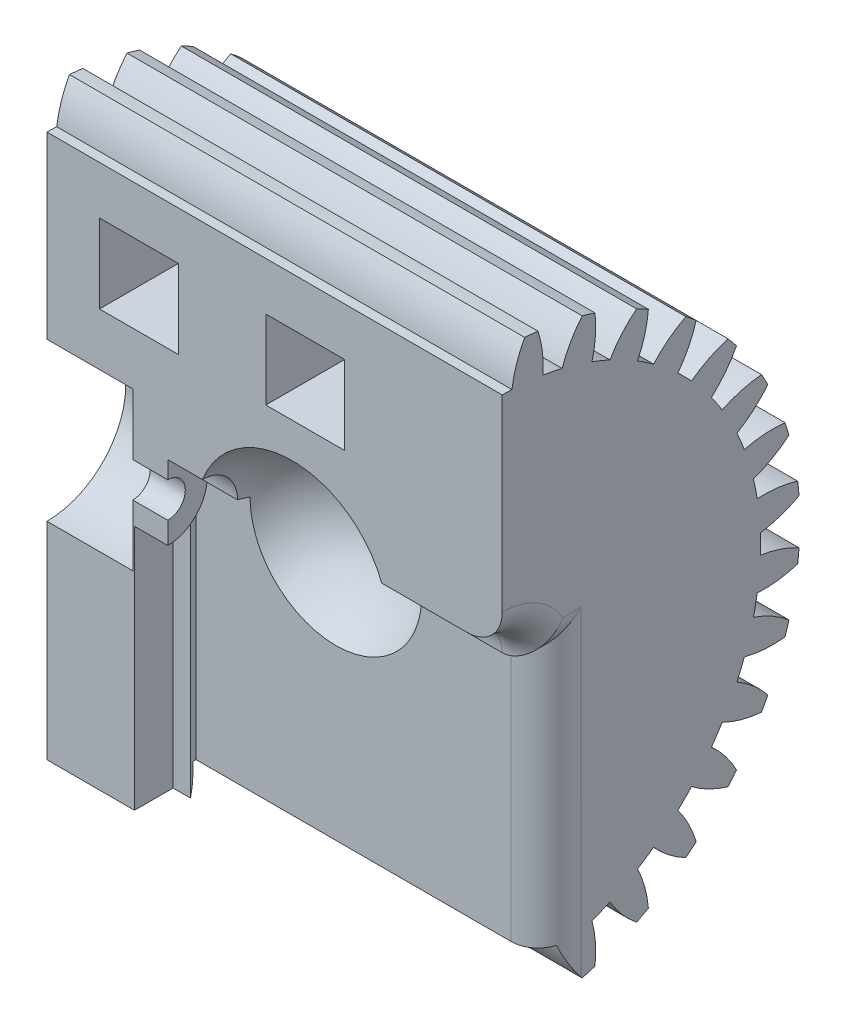
SolidWorks part; units mm, degrees
ref_plane "Plane1" through (0, 0, 0) normal (0, 0, 1) x (1, 0, 0)
ref_plane "Plane2" through (0, 0, 0) normal (0, 1, 0) x (1, 0, 0)
ref_plane "Plane3" through (0, 0, 0) normal (1, 0, 0) x (0, 0, -1)
other "Configuration Table"
sketch "HoldingSke" plane through (0, 0, 0) normal (0, 1, 0) x (1, 0, 0)
  line L0 (0, 0) -> (1.6961, -1.0598)
  line L1 (-15, 0) -> (100, 0) construction
  line L2 (0, 0) -> (-2.1039, 2.3779)
  line L3 (0, 0) -> (-11.863, 4.5341)
  line L4 (0, 0) -> (7.3237, 4.5764)
  line L5 (0, 0) -> (-46.8476, -17.4728)
  line L6 (0, 0) -> (-8.2896, -5.593)
  line L7 (-2.1039, 2.3779) -> (8.6586, 51.2059)
  line L8 (-76.2, 54.61) -> (-75.9, 54.61)
  line L9 (-67.7845, 28.3722) -> (-49.3413, 33.142)
  line L10 (-76.2, 71.12) -> (104.1128, 71.12)
  line L11 (0, 0) -> (-10, 0)
  line L12 (-76.2, 101.6) -> (-76.181, 101.6)
  line L13 (24.9733, 27.94) -> (52.9518, 28.4284)
  line L14 (24.9733, 27.94) -> (24.9743, 27.94)
  line L15 (24.9733, 27.94) -> (100.4006, 29.5858)
  line L16 (-63.627, -0.5) -> (-12.827, -0.5)
  circle A0 centre (0, 0) radius 1
  circle A1 centre (0, 0) radius 7.374
  circle A2 centre (0, 0) radius 37.5
  circle A3 centre (0, 0) radius 1
  dimension "Num_teeth" = 32
  dimension "Pitch_radius" = 180.3128
  dimension "Width" = 10
  dimension "Thickness" = 10
sketch "BasProSke" plane through (0, 0, 0) normal (0, 1, 0) x (1, 0, 0)
  line L0 (-10, 0) -> (60, 0) construction
  line L1 (0, 0) -> (0, 8.5)
  line L2 (0, 0) -> (10, 0)
  line L3 (10, 0) -> (10, 8.5)
  line L4 (10, 8.5) -> (0, 8.5)
  dimension "Thickness" = 10
  dimension "Diameter" = 17
revolve "Base-Revolve" add sketch "BasProSke" angle 360 about L0
sketch "TooCutSke" plane through (0, 0, 0) normal (1, 0, 0) x (0, 0, -1)
  line L1 (0, 0) -> (0, 107) construction
  line L2 (0, 0) -> (-0.4258, 7.9887) construction
  line L3 (0, 0) -> (-1.5667, 15.9069) construction
  line L4 (-0.4258, 7.9887) -> (-0.7833, 7.9534) construction
  arc A0 (0.277, 7.3688) -> (-0.277, 7.3688) centre (0, 0) ccw
  arc A1 (0.6561, 8.5001) -> (-0.6561, 8.5001) centre (0, 0) ccw
  circle A2 centre (0, 0) radius 8 construction
  circle A3 centre (0, 0) radius 7.7452 construction
  arc A4 (-0.277, 7.3688) -> (-0.6561, 8.5001) centre (-3.4475, 6.9356) ccw
  arc A5 (0.6561, 8.5001) -> (0.277, 7.3688) centre (3.4475, 6.9356) ccw
extrude "ToothCut" cut sketch "TooCutSke" along normal through all
fillet "Breaks" [suppressed] radius 0.01 tangent propagation no
fillet "RootFillets" [suppressed] radius 0.126
pattern_circular "TeethCuts" count 32 every 11.25 about axis through (-10, 0, 0) along (1, 0, 0) of "ToothCut", "RootFillets", "Breaks"
sketch "HubNeaOneSke" plane through (0, 0, 0) normal (-1, 0, 0) x (0, 0, 1)
  circle A0 centre (0, 0) radius 7.374
  dimension "Diameter" = 14.748
extrude "HubNearOne" [suppressed] add sketch "HubNeaOneSke" along normal blind 40.0001
sketch "HubNeaBotSke" plane through (0, 0, 0) normal (-1, 0, 0) x (0, 0, 1)
  circle A0 centre (0, 0) radius 7.374
  dimension "Diameter" = 14.748
extrude "HubNearBoth" [suppressed] add sketch "HubNeaBotSke" along normal blind 20
ref_plane "FarPln" through (10, 0, 0) normal (1, 0, 0) x (0, 0, -1)
sketch "HubFarSke" plane through (10, 0, 0) normal (1, 0, 0) x (0, 0, -1)
  circle A0 centre (0, 0) radius 7.374
  dimension "Diameter" = 14.748
extrude "HubFar" [suppressed] add sketch "HubFarSke" along normal blind 20
sketch "BorSke" plane through (0, 0, 0) normal (1, 0, 0) x (0, 0, -1)
  circle A0 centre (0, 0) radius 1
  dimension "Diameter" = 2
extrude "Bore" cut sketch "BorSke" along normal mid plane 100.0001
sketch "KeySke" plane through (0, 0, 0) normal (1, 0, 0) x (0, 0, -1)
  line L0 (-0.4, 0) -> (-0.4, 1.3)
  line L1 (-0.4, 1.3) -> (0.4, 1.3)
  line L2 (0.4, 1.3) -> (0.4, 0)
  line L3 (0, 0) -> (0, 34) construction
  line L4 (-0.4, 0) -> (0.4, 0)
  dimension "Width" = 0.8
extrude "Keyway" [suppressed] cut sketch "KeySke" along normal mid plane 100.0001
pattern_circular "Keyway2" [suppressed] count 2 every 90 about axis through (-10, 0, 0) along (1, 0, 0) reverse direction yes
sketch "Sketch1" plane through (10, 0, 0) normal (1, 0, 0) x (0, 0, -1)
  line L1 (-1.1, 0) -> (1.1, 0)
  line L2 (-1.1, 0) -> (-1.1, -12)
  line L3 (-1.1, -12) -> (1.1, -12)
  line L4 (1.1, 0) -> (1.1, -12)
  circle A0 centre (0, 0) radius 1 construction
  dimension "D3" = 12
  dimension "D1" = 2.2
  dimension "D2" = 1.1
  dimension "D4" = 12
extrude "Cut-Extrude1" cut sketch "Sketch1" against normal through all
sketch "Sketch2" plane through (0, 0, 0) normal (0, 0, 1) x (1, 0, 0)
  line L3 (4.25, 0) -> (9.75, 0)
  arc A0 (9.75, 0) -> (4.25, 0) centre (7, 0) ccw
  dimension "D2" = 5.5
  dimension "D1" = 7
revolve "Cut-Revolve1" cut sketch "Sketch2" angle 360 about L3
ref_plane "Plane4" through (3, 0, 0) normal (-1, 0, 0) x (0, 0, 1)
sketch "Sketch4" plane through (3, 0, 0) normal (-1, 0, 0) x (0, 0, 1)
  circle A0 centre (0, 0) radius 1.125
  circle A1 centre (0, 0) radius 0.5
  dimension "D1" = 1
extrude "Boss-Extrude1" add sketch "Sketch4" along normal blind 0.5
sketch "Sketch5" plane through (0, 0, -1.1) normal (0, 0, 1) x (1, 0, 0)
  line L0 (0, -8.1488) -> (10, -8.1488) construction
  line L1 (0, 0) -> (2.5, 0)
  line L2 (0, 0) -> (0, -8.1488)
  line L3 (0, -8.1488) -> (2.5, -8.1488)
  line L4 (2.5, 0) -> (2.5, -8.1488)
  dimension "D1" = 2.5
extrude "Boss-Extrude2" add sketch "Sketch5" along normal up to next
sketch "Sketch6" plane through (0, 0, 0) normal (-1, 0, 0) x (0, 0, 1)
  line L0 (1, 0) -> (-1, 0) construction
  circle A0 centre (0, 0) radius 2.25
  dimension "D1" = 4.5
extrude "Cut-Extrude4" cut sketch "Sketch6" against normal blind 2.45
sketch "Sketch7" plane through (2.5, 0, 0) normal (1, 0, 0) x (0, 0, -1)
  circle A0 centre (0, 0) radius 0.5
extrude "Cut-Extrude5" cut sketch "Sketch7" against normal blind 2.4
sketch "Sketch8" plane through (0, 0, 0) normal (0, 0, 1) x (1, 0, 0)
  line L1 (-0.5092, 8.9097) -> (10.5538, 8.9097)
  line L2 (-0.5092, 8.9097) -> (-0.5092, -8.8891)
  line L3 (-0.5092, -8.8891) -> (10.5538, -8.8891)
  line L4 (10.5538, 8.9097) -> (10.5538, -8.8891)
extrude "Cut-Extrude7" cut sketch "Sketch8" along normal blind 10
sketch "Sketch9" plane through (0, 0, 0) normal (0, 0, 1) x (1, 0, 0)
  line L0 (10, 1) -> (10, 7.374) construction
  line L1 (1.5, 6) -> (3.75, 6)
  line L2 (1.5, 6) -> (1.5, 3.75)
  line L3 (1.5, 3.75) -> (3.75, 3.75)
  line L4 (3.75, 6) -> (3.75, 3.75)
  line L5 (6.25, 6) -> (8.5, 6)
  line L6 (6.25, 6) -> (6.25, 3.75)
  line L7 (6.25, 3.75) -> (8.5, 3.75)
  line L8 (8.5, 6) -> (8.5, 3.75)
  line L9 (0, 7.374) -> (0, 2.25) construction
  line L10 (0, 2.25) -> (0, -2.25) construction
  point P14 (0, 0)
  dimension "D1" = 2.25
  dimension "D2" = 2.25
  dimension "D3" = 2.25
  dimension "D4" = 2.25
  dimension "D5" = 1.5
  dimension "D6" = 1.5
  dimension "D7" = 3.75
  dimension "D8" = 3.75
extrude "Cut-Extrude8" cut sketch "Sketch9" against normal blind 2.25
sketch "Sketch10" plane through (10, 0, 0) normal (1, 0, 0) x (0, 0, -1)
  line L1 (0, 0) -> (1.25, 0)
  line L2 (0, 0) -> (0, -9)
  line L3 (0, -9) -> (1.25, -9)
  line L4 (1.25, 0) -> (1.25, -9)
  dimension "D1" = 1.25
  dimension "D2" = 9
extrude "Cut-Extrude10" cut sketch "Sketch10" against normal blind 7 contours L2 L1 L4 L3
ref_plane "Plane5" through (12, 0, 0) normal (1, 0, 0) x (0, 0, -1)
sketch "Sketch11" plane through (12, 0, 0) normal (1, 0, 0) x (0, 0, -1)
  line L0 (0, 1) -> (0, 7.374) construction
  line L1 (1.25, 0) -> (1, 0) construction
  line L2 (1.25, 0) -> (1.25, -7.2673) construction
  line L3 (0, 1) -> (0, 7.374)
  line L4 (1.25, 0) -> (1, 0)
  line L5 (1.25, 0) -> (1.25, -7.2673)
  arc A0 (2.564, 6.9139) -> (2.6499, 8.0764) centre (-0.531, 7.727) ccw construction
  arc A1 (8.0764, -2.6499) -> (8.1875, -2.2837) centre (0, 0) ccw construction
  arc A2 (8.4382, -1.0233) -> (8.4757, -0.6425) centre (0, 0) ccw construction
  arc A3 (8.1875, 2.2837) -> (8.0764, 2.6499) centre (0, 0) ccw construction
  arc A4 (7.5846, 3.8371) -> (7.4042, 4.1746) centre (0, 0) ccw construction
  arc A5 (6.6903, 5.2431) -> (6.4475, 5.5389) centre (0, 0) ccw construction
  arc A6 (5.5389, 6.4475) -> (5.2431, 6.6903) centre (0, 0) ccw construction
  arc A7 (2.6499, 8.0764) -> (2.2837, 8.1875) centre (0, 0) ccw construction
  arc A8 (4.1746, 7.4042) -> (3.8371, 7.5846) centre (0, 0) ccw construction
  arc A9 (3.8371, 7.5846) -> (3.0758, 6.7019) centre (5.8392, 5.0883) ccw construction
  arc A10 (2.2837, 8.1875) -> (1.7093, 7.1732) centre (4.7344, 6.1297) ccw construction
  arc A11 (3.8636, 6.2808) -> (4.1746, 7.4042) centre (0.9867, 7.6821) ccw construction
  arc A12 (5.2431, 6.6903) -> (4.3242, 5.973) centre (6.7197, 3.8514) ccw construction
  arc A13 (5.0147, 5.4064) -> (5.5389, 6.4475) centre (2.4664, 7.342) ccw construction
  arc A14 (6.4475, 5.5389) -> (5.4064, 5.0147) centre (7.342, 2.4664) ccw construction
  arc A15 (5.973, 4.3242) -> (6.6903, 5.2431) centre (3.8514, 6.7197) ccw construction
  arc A16 (7.4042, 4.1746) -> (6.2808, 3.8636) centre (7.6821, 0.9867) ccw construction
  arc A17 (6.7019, 3.0758) -> (7.5846, 3.8371) centre (5.0883, 5.8392) ccw construction
  arc A18 (8.0764, 2.6499) -> (6.9139, 2.564) centre (7.727, -0.531) ccw construction
  arc A19 (7.1732, 1.7093) -> (8.1875, 2.2837) centre (6.1297, 4.7344) ccw construction
  arc A20 (8.4382, 1.0233) -> (7.2812, 1.1659) centre (7.4749, -2.0282) ccw construction
  arc A21 (8.4757, 0.6425) -> (8.4382, 1.0233) centre (0, 0) ccw construction
  arc A22 (7.3688, 0.277) -> (8.4757, 0.6425) centre (6.9356, 3.4475) ccw construction
  arc A23 (8.4757, -0.6425) -> (7.3688, -0.277) centre (6.9356, -3.4475) ccw construction
  arc A24 (7.2812, -1.1659) -> (8.4382, -1.0233) centre (7.4749, 2.0282) ccw construction
  arc A25 (8.1875, -2.2837) -> (7.1732, -1.7093) centre (6.1297, -4.7344) ccw construction
  arc A26 (6.9139, -2.564) -> (8.0764, -2.6499) centre (7.727, 0.531) ccw construction
  arc A27 (7.4042, -4.1746) -> (7.5846, -3.8371) centre (0, 0) ccw construction
  arc A28 (7.5846, -3.8371) -> (6.7019, -3.0758) centre (5.0883, -5.8392) ccw construction
  arc A29 (6.2808, -3.8636) -> (7.4042, -4.1746) centre (7.6821, -0.9867) ccw construction
  arc A30 (6.6903, -5.2431) -> (5.973, -4.3242) centre (3.8514, -6.7197) ccw construction
  arc A31 (6.4475, -5.5389) -> (6.6903, -5.2431) centre (0, 0) ccw construction
  arc A32 (5.4064, -5.0147) -> (6.4475, -5.5389) centre (7.342, -2.4664) ccw construction
  arc A33 (5.5389, -6.4475) -> (5.0147, -5.4064) centre (2.4664, -7.342) ccw construction
  arc A34 (5.2431, -6.6903) -> (5.5389, -6.4475) centre (0, 0) ccw construction
  arc A35 (4.3242, -5.973) -> (5.2431, -6.6903) centre (6.7197, -3.8514) ccw construction
  arc A36 (4.1746, -7.4042) -> (3.8636, -6.2808) centre (0.9867, -7.6821) ccw construction
  arc A37 (3.8371, -7.5846) -> (4.1746, -7.4042) centre (0, 0) ccw construction
  arc A38 (3.0758, -6.7019) -> (3.8371, -7.5846) centre (5.8392, -5.0883) ccw construction
  arc A39 (2.6499, -8.0764) -> (2.564, -6.9139) centre (-0.531, -7.727) ccw construction
  arc A40 (2.2837, -8.1875) -> (2.6499, -8.0764) centre (0, 0) ccw construction
  arc A41 (1.7093, -7.1732) -> (2.2837, -8.1875) centre (4.7344, -6.1297) ccw construction
  arc A42 (1.25, -7.2673) -> (1.7093, -7.1732) centre (0, 0) ccw construction
  arc A43 (2.564, -6.9139) -> (3.0758, -6.7019) centre (0, 0) ccw construction
  arc A44 (3.8636, -6.2808) -> (4.3242, -5.973) centre (0, 0) ccw construction
  arc A45 (5.0147, -5.4064) -> (5.4064, -5.0147) centre (0, 0) ccw construction
  arc A46 (5.973, -4.3242) -> (6.2808, -3.8636) centre (0, 0) ccw construction
  arc A47 (6.7019, -3.0758) -> (6.9139, -2.564) centre (0, 0) ccw construction
  arc A48 (7.1732, -1.7093) -> (7.2812, -1.1659) centre (0, 0) ccw construction
  arc A49 (7.3688, -0.277) -> (7.3688, 0.277) centre (0, 0) ccw construction
  arc A50 (7.2812, 1.1659) -> (7.1732, 1.7093) centre (0, 0) ccw construction
  arc A51 (6.9139, 2.564) -> (6.7019, 3.0758) centre (0, 0) ccw construction
  arc A52 (6.2808, 3.8636) -> (5.973, 4.3242) centre (0, 0) ccw construction
  arc A53 (5.4064, 5.0147) -> (5.0147, 5.4064) centre (0, 0) ccw construction
  arc A54 (4.3242, 5.973) -> (3.8636, 6.2808) centre (0, 0) ccw construction
  arc A55 (3.0758, 6.7019) -> (2.564, 6.9139) centre (0, 0) ccw construction
  arc A56 (1.7093, 7.1732) -> (1.1659, 7.2812) centre (0, 0) ccw construction
  arc A57 (1.0233, 8.4382) -> (0.6425, 8.4757) centre (0, 0) ccw construction
  arc A58 (1.1659, 7.2812) -> (1.0233, 8.4382) centre (-2.0282, 7.4749) ccw construction
  arc A59 (0.6425, 8.4757) -> (0.277, 7.3688) centre (3.4475, 6.9356) ccw construction
  arc A60 (0.277, 7.3688) -> (0, 7.374) centre (0, 0) ccw construction
  arc A61 (1, 0) -> (0, 1) centre (0, 0) ccw construction
  arc A62 (2.564, 6.9139) -> (2.6499, 8.0764) centre (-0.531, 7.727) ccw
  arc A63 (8.0764, -2.6499) -> (8.1875, -2.2837) centre (0, 0) ccw
  arc A64 (8.4382, -1.0233) -> (8.4757, -0.6425) centre (0, 0) ccw
  arc A65 (8.1875, 2.2837) -> (8.0764, 2.6499) centre (0, 0) ccw
  arc A66 (7.5846, 3.8371) -> (7.4042, 4.1746) centre (0, 0) ccw
  arc A67 (6.6903, 5.2431) -> (6.4475, 5.5389) centre (0, 0) ccw
  arc A68 (5.5389, 6.4475) -> (5.2431, 6.6903) centre (0, 0) ccw
  arc A69 (2.6499, 8.0764) -> (2.2837, 8.1875) centre (0, 0) ccw
  arc A70 (4.1746, 7.4042) -> (3.8371, 7.5846) centre (0, 0) ccw
  arc A71 (3.8371, 7.5846) -> (3.0758, 6.7019) centre (5.8392, 5.0883) ccw
  arc A72 (2.2837, 8.1875) -> (1.7093, 7.1732) centre (4.7344, 6.1297) ccw
  arc A73 (3.8636, 6.2808) -> (4.1746, 7.4042) centre (0.9867, 7.6821) ccw
  arc A74 (5.2431, 6.6903) -> (4.3242, 5.973) centre (6.7197, 3.8514) ccw
  arc A75 (5.0147, 5.4064) -> (5.5389, 6.4475) centre (2.4664, 7.342) ccw
  arc A76 (6.4475, 5.5389) -> (5.4064, 5.0147) centre (7.342, 2.4664) ccw
  arc A77 (5.973, 4.3242) -> (6.6903, 5.2431) centre (3.8514, 6.7197) ccw
  arc A78 (7.4042, 4.1746) -> (6.2808, 3.8636) centre (7.6821, 0.9867) ccw
  arc A79 (6.7019, 3.0758) -> (7.5846, 3.8371) centre (5.0883, 5.8392) ccw
  arc A80 (8.0764, 2.6499) -> (6.9139, 2.564) centre (7.727, -0.531) ccw
  arc A81 (7.1732, 1.7093) -> (8.1875, 2.2837) centre (6.1297, 4.7344) ccw
  arc A82 (8.4382, 1.0233) -> (7.2812, 1.1659) centre (7.4749, -2.0282) ccw
  arc A83 (8.4757, 0.6425) -> (8.4382, 1.0233) centre (0, 0) ccw
  arc A84 (7.3688, 0.277) -> (8.4757, 0.6425) centre (6.9356, 3.4475) ccw
  arc A85 (8.4757, -0.6425) -> (7.3688, -0.277) centre (6.9356, -3.4475) ccw
  arc A86 (7.2812, -1.1659) -> (8.4382, -1.0233) centre (7.4749, 2.0282) ccw
  arc A87 (8.1875, -2.2837) -> (7.1732, -1.7093) centre (6.1297, -4.7344) ccw
  arc A88 (6.9139, -2.564) -> (8.0764, -2.6499) centre (7.727, 0.531) ccw
  arc A89 (7.4042, -4.1746) -> (7.5846, -3.8371) centre (0, 0) ccw
  arc A90 (7.5846, -3.8371) -> (6.7019, -3.0758) centre (5.0883, -5.8392) ccw
  arc A91 (6.2808, -3.8636) -> (7.4042, -4.1746) centre (7.6821, -0.9867) ccw
  arc A92 (6.6903, -5.2431) -> (5.973, -4.3242) centre (3.8514, -6.7197) ccw
  arc A93 (6.4475, -5.5389) -> (6.6903, -5.2431) centre (0, 0) ccw
  arc A94 (5.4064, -5.0147) -> (6.4475, -5.5389) centre (7.342, -2.4664) ccw
  arc A95 (5.5389, -6.4475) -> (5.0147, -5.4064) centre (2.4664, -7.342) ccw
  arc A96 (5.2431, -6.6903) -> (5.5389, -6.4475) centre (0, 0) ccw
  arc A97 (4.3242, -5.973) -> (5.2431, -6.6903) centre (6.7197, -3.8514) ccw
  arc A98 (4.1746, -7.4042) -> (3.8636, -6.2808) centre (0.9867, -7.6821) ccw
  arc A99 (3.8371, -7.5846) -> (4.1746, -7.4042) centre (0, 0) ccw
  arc A100 (3.0758, -6.7019) -> (3.8371, -7.5846) centre (5.8392, -5.0883) ccw
  arc A101 (2.6499, -8.0764) -> (2.564, -6.9139) centre (-0.531, -7.727) ccw
  arc A102 (2.2837, -8.1875) -> (2.6499, -8.0764) centre (0, 0) ccw
  arc A103 (1.7093, -7.1732) -> (2.2837, -8.1875) centre (4.7344, -6.1297) ccw
  arc A104 (1.25, -7.2673) -> (1.7093, -7.1732) centre (0, 0) ccw
  arc A105 (2.564, -6.9139) -> (3.0758, -6.7019) centre (0, 0) ccw
  arc A106 (3.8636, -6.2808) -> (4.3242, -5.973) centre (0, 0) ccw
  arc A107 (5.0147, -5.4064) -> (5.4064, -5.0147) centre (0, 0) ccw
  arc A108 (5.973, -4.3242) -> (6.2808, -3.8636) centre (0, 0) ccw
  arc A109 (6.7019, -3.0758) -> (6.9139, -2.564) centre (0, 0) ccw
  arc A110 (7.1732, -1.7093) -> (7.2812, -1.1659) centre (0, 0) ccw
  arc A111 (7.3688, -0.277) -> (7.3688, 0.277) centre (0, 0) ccw
  arc A112 (7.2812, 1.1659) -> (7.1732, 1.7093) centre (0, 0) ccw
  arc A113 (6.9139, 2.564) -> (6.7019, 3.0758) centre (0, 0) ccw
  arc A114 (6.2808, 3.8636) -> (5.973, 4.3242) centre (0, 0) ccw
  arc A115 (5.4064, 5.0147) -> (5.0147, 5.4064) centre (0, 0) ccw
  arc A116 (4.3242, 5.973) -> (3.8636, 6.2808) centre (0, 0) ccw
  arc A117 (3.0758, 6.7019) -> (2.564, 6.9139) centre (0, 0) ccw
  arc A118 (1.7093, 7.1732) -> (1.1659, 7.2812) centre (0, 0) ccw
  arc A119 (1.0233, 8.4382) -> (0.6425, 8.4757) centre (0, 0) ccw
  arc A120 (1.1659, 7.2812) -> (1.0233, 8.4382) centre (-2.0282, 7.4749) ccw
  arc A121 (0.6425, 8.4757) -> (0.277, 7.3688) centre (3.4475, 6.9356) ccw
  arc A122 (0.277, 7.3688) -> (0, 7.374) centre (0, 0) ccw
  arc A123 (1, 0) -> (0, 1) centre (0, 0) ccw
extrude "Boss-Extrude3" add sketch "Sketch11" against normal up to next
ref_plane "Plane6" through (13, 0, 0) normal (1, 0, 0) x (0, 0, -1)
sketch "Sketch14" plane through (13, 0, 0) normal (1, 0, 0) x (0, 0, -1)
  line L3 (0, 1) -> (0, 7.374)
  line L4 (1.25, 0) -> (1, 0)
  line L5 (1.25, 0) -> (1.25, -7.2673)
  arc A62 (2.564, 6.9139) -> (2.6499, 8.0764) centre (-0.531, 7.727) ccw
  arc A63 (8.0764, -2.6499) -> (8.1875, -2.2837) centre (0, 0) ccw
  arc A64 (8.4382, -1.0233) -> (8.4757, -0.6425) centre (0, 0) ccw
  arc A65 (8.1875, 2.2837) -> (8.0764, 2.6499) centre (0, 0) ccw
  arc A66 (7.5846, 3.8371) -> (7.4042, 4.1746) centre (0, 0) ccw
  arc A67 (6.6903, 5.2431) -> (6.4475, 5.5389) centre (0, 0) ccw
  arc A68 (5.5389, 6.4475) -> (5.2431, 6.6903) centre (0, 0) ccw
  arc A69 (2.6499, 8.0764) -> (2.2837, 8.1875) centre (0, 0) ccw
  arc A70 (4.1746, 7.4042) -> (3.8371, 7.5846) centre (0, 0) ccw
  arc A71 (3.8371, 7.5846) -> (3.0758, 6.7019) centre (5.8392, 5.0883) ccw
  arc A72 (2.2837, 8.1875) -> (1.7093, 7.1732) centre (4.7344, 6.1297) ccw
  arc A73 (3.8636, 6.2808) -> (4.1746, 7.4042) centre (0.9867, 7.6821) ccw
  arc A74 (5.2431, 6.6903) -> (4.3242, 5.973) centre (6.7197, 3.8514) ccw
  arc A75 (5.0147, 5.4064) -> (5.5389, 6.4475) centre (2.4664, 7.342) ccw
  arc A76 (6.4475, 5.5389) -> (5.4064, 5.0147) centre (7.342, 2.4664) ccw
  arc A77 (5.973, 4.3242) -> (6.6903, 5.2431) centre (3.8514, 6.7197) ccw
  arc A78 (7.4042, 4.1746) -> (6.2808, 3.8636) centre (7.6821, 0.9867) ccw
  arc A79 (6.7019, 3.0758) -> (7.5846, 3.8371) centre (5.0883, 5.8392) ccw
  arc A80 (8.0764, 2.6499) -> (6.9139, 2.564) centre (7.727, -0.531) ccw
  arc A81 (7.1732, 1.7093) -> (8.1875, 2.2837) centre (6.1297, 4.7344) ccw
  arc A82 (8.4382, 1.0233) -> (7.2812, 1.1659) centre (7.4749, -2.0282) ccw
  arc A83 (8.4757, 0.6425) -> (8.4382, 1.0233) centre (0, 0) ccw
  arc A84 (7.3688, 0.277) -> (8.4757, 0.6425) centre (6.9356, 3.4475) ccw
  arc A85 (8.4757, -0.6425) -> (7.3688, -0.277) centre (6.9356, -3.4475) ccw
  arc A86 (7.2812, -1.1659) -> (8.4382, -1.0233) centre (7.4749, 2.0282) ccw
  arc A87 (8.1875, -2.2837) -> (7.1732, -1.7093) centre (6.1297, -4.7344) ccw
  arc A88 (6.9139, -2.564) -> (8.0764, -2.6499) centre (7.727, 0.531) ccw
  arc A89 (7.4042, -4.1746) -> (7.5846, -3.8371) centre (0, 0) ccw
  arc A90 (7.5846, -3.8371) -> (6.7019, -3.0758) centre (5.0883, -5.8392) ccw
  arc A91 (6.2808, -3.8636) -> (7.4042, -4.1746) centre (7.6821, -0.9867) ccw
  arc A92 (6.6903, -5.2431) -> (5.973, -4.3242) centre (3.8514, -6.7197) ccw
  arc A93 (6.4475, -5.5389) -> (6.6903, -5.2431) centre (0, 0) ccw
  arc A94 (5.4064, -5.0147) -> (6.4475, -5.5389) centre (7.342, -2.4664) ccw
  arc A95 (5.5389, -6.4475) -> (5.0147, -5.4064) centre (2.4664, -7.342) ccw
  arc A96 (5.2431, -6.6903) -> (5.5389, -6.4475) centre (0, 0) ccw
  arc A97 (4.3242, -5.973) -> (5.2431, -6.6903) centre (6.7197, -3.8514) ccw
  arc A98 (4.1746, -7.4042) -> (3.8636, -6.2808) centre (0.9867, -7.6821) ccw
  arc A99 (3.8371, -7.5846) -> (4.1746, -7.4042) centre (0, 0) ccw
  arc A100 (3.0758, -6.7019) -> (3.8371, -7.5846) centre (5.8392, -5.0883) ccw
  arc A101 (2.6499, -8.0764) -> (2.564, -6.9139) centre (-0.531, -7.727) ccw
  arc A102 (2.2837, -8.1875) -> (2.6499, -8.0764) centre (0, 0) ccw
  arc A103 (1.7093, -7.1732) -> (2.2837, -8.1875) centre (4.7344, -6.1297) ccw
  arc A104 (1.25, -7.2673) -> (1.7093, -7.1732) centre (0, 0) ccw
  arc A105 (2.564, -6.9139) -> (3.0758, -6.7019) centre (0, 0) ccw
  arc A106 (3.8636, -6.2808) -> (4.3242, -5.973) centre (0, 0) ccw
  arc A107 (5.0147, -5.4064) -> (5.4064, -5.0147) centre (0, 0) ccw
  arc A108 (5.973, -4.3242) -> (6.2808, -3.8636) centre (0, 0) ccw
  arc A109 (6.7019, -3.0758) -> (6.9139, -2.564) centre (0, 0) ccw
  arc A110 (7.1732, -1.7093) -> (7.2812, -1.1659) centre (0, 0) ccw
  arc A111 (7.3688, -0.277) -> (7.3688, 0.277) centre (0, 0) ccw
  arc A112 (7.2812, 1.1659) -> (7.1732, 1.7093) centre (0, 0) ccw
  arc A113 (6.9139, 2.564) -> (6.7019, 3.0758) centre (0, 0) ccw
  arc A114 (6.2808, 3.8636) -> (5.973, 4.3242) centre (0, 0) ccw
  arc A115 (5.4064, 5.0147) -> (5.0147, 5.4064) centre (0, 0) ccw
  arc A116 (4.3242, 5.973) -> (3.8636, 6.2808) centre (0, 0) ccw
  arc A117 (3.0758, 6.7019) -> (2.564, 6.9139) centre (0, 0) ccw
  arc A118 (1.7093, 7.1732) -> (1.1659, 7.2812) centre (0, 0) ccw
  arc A119 (1.0233, 8.4382) -> (0.6425, 8.4757) centre (0, 0) ccw
  arc A120 (1.1659, 7.2812) -> (1.0233, 8.4382) centre (-2.0282, 7.4749) ccw
  arc A121 (0.6425, 8.4757) -> (0.277, 7.3688) centre (3.4475, 6.9356) ccw
  arc A122 (0.277, 7.3688) -> (0, 7.374) centre (0, 0) ccw
  arc A123 (1, 0) -> (0, 1) centre (0, 0) ccw
extrude "Boss-Extrude4" add sketch "Sketch14" against normal blind 1.25
sketch "Sketch15" plane through (2.45, 0, 0) normal (-1, 0, 0) x (0, 0, 1)
  line L0 (0, 1.125) -> (0, 0.5)
  line L1 (0, -1.125) -> (0, -0.5)
  line L2 (0, -2.25) -> (0, -0.5) construction
  line L3 (0, 1) -> (0, 2.25) construction
  arc A0 (0, -0.5) -> (0, 0.5) centre (0, 0) cw
  arc A1 (0, 0.5) -> (-0.5, 0) centre (0, 0) ccw construction
  arc A2 (0, -1.125) -> (0, 1.125) centre (0, 0) cw
  dimension "D1" = 1.125
extrude "Boss-Extrude5" add sketch "Sketch15" against normal blind 1
fillet "Fillet1" radius 1 3 edges at (13, 0, -1.125) (13, 0.7071, -0.7071) (13, -3.6336, -1.25)
equation "' \"Module@HoldingSke\" = 6.35"
equation "' \"Num_teeth@HoldingSke\" = 12"
equation "' \"Ap@HoldingSke\" =  20"
equation "' \"Ap@HoldingSke\" = 20"
equation "' \"Width@HoldingSke\" = 0.5 * 25.4"
equation "' \"Hub_dia@HoldingSke\"= 1 * 25.4"
equation "' \"Hub_dia@HoldingSke\" = 1 * 25.4"
equation "' \"Overall_len@HoldingSke\" = 1.0 * 25.4"
equation "' \"Bore@HoldingSke\" = 0.75 * 25.4"
equation "' \"T_dim@HoldingSke\" = 0.1 * 25.4"
equation "' \"Width@KeySke\" = 0.25 * 25.4"
equation "' \"Show_teeth@HoldingSke\" = 13"
equation "' \"Backlash@HoldingSke\" = 0.009 * 25.4"
equation "' \"Addendum_fac@HoldingSke\" = 1.0"
equation "' \"Dedendum_fac@HoldingSke\" = 1.25"
equation "' \"Dedendum_add@HoldingSke\" = 0.00005 * 25.4"
equation "' \"Clearance_fac@HoldingSke\" = 0.25"
equation "\"Pitch@HoldingSke\" = 1 / \"Module@HoldingSke\""
equation "\"Overcut_dia@TooCutSke\" = (\"Num_teeth@HoldingSke\" + 2 * \"Addendum_fac@HoldingSke\") / \"Pitch@HoldingSke\" + 0.002 * 25.4"
equation "\"Pitch_dia@TooCutSke\" = \"Num_teeth@HoldingSke\" / \"Pitch@HoldingSke\""
equation "\"Base_dia@TooCutSke\" = \"Num_teeth@HoldingSke\" / \"Pitch@HoldingSke\" * cos((\"Ap@HoldingSke\"  * 3.14159265 / 180))"
equation "\"Root_dia@TooCutSke\" = (\"Num_teeth@HoldingSke\" + 2) / \"Pitch@HoldingSke\" - 2 * (\"Addendum_fac@HoldingSke\" + \"Dedendum_fac@HoldingSke\") / \"Pitch@HoldingSke\" - \"Dedendum_add@HoldingSke\" * 2"
equation "\"Half_ang@TooCutSke\" = 180 / \"Num_teeth@HoldingSke\""
equation "\"Half_CT@TooCutSke\" = \"Num_teeth@HoldingSke\" / \"Pitch@HoldingSke\" * sin((3.14159265 / 2 / \"Num_teeth@HoldingSke\")) / 2 - 7 * \"Backlash@HoldingSke\" / 4"
equation "\"Flank_rad@TooCutSke\" = \"Num_teeth@HoldingSke\" / \"Pitch@HoldingSke\" / 5"
equation "\"Radius@RootFillets\" = \"Clearance_fac@HoldingSke\" / \"Pitch@HoldingSke\" + \"Dedendum_add@HoldingSke\""
equation "\"Break_rad@Breaks\" = 0.02 / \"Pitch@HoldingSke\""
equation "\"Thickness@HoldingSke\" = \"Width@HoldingSke\""
equation "\"OAL@HoldingSke\" = \"Thickness@HoldingSke\""
equation "\"MHD@HoldingSke\" = (\"Num_teeth@HoldingSke\" + 2) / \"Pitch@HoldingSke\" - 2 * (\"Addendum_fac@HoldingSke\" + \"Dedendum_fac@HoldingSke\")  / \"Pitch@HoldingSke\" - \"Dedendum_add@HoldingSke\" * 2"
equation "\"MBD@HoldingSke\" = (\"Num_teeth@HoldingSke\" + 2) / \"Pitch@HoldingSke\" - 2 * (\"Addendum_fac@HoldingSke\" + \"Dedendum_fac@HoldingSke\")  / \"Pitch@HoldingSke\" - \"Dedendum_add@HoldingSke\" * 2 - 0.002 * 25.4"
equation "\"MHD@HoldingSke\" = ((sgn( \"MHD@HoldingSke\" - \"Hub_dia@HoldingSke\" )-1)*( \"MHD@HoldingSke\" - \"Hub_dia@HoldingSke\" ))/-2+ \"Hub_dia@HoldingSke\""
equation "\"MBD@HoldingSke\" = ((sgn( \"MBD@HoldingSke\" - \"Bore@HoldingSke\" )-1)*( \"MBD@HoldingSke\" - \"Bore@HoldingSke\" ))/-2+ \"Bore@HoldingSke\""
equation "\"OAL@HoldingSke\" = ((sgn( \"OAL@HoldingSke\" - \"Overall_len@HoldingSke\" )+1)*( \"OAL@HoldingSke\" - \"Overall_len@HoldingSke\" ))/2 + \"Overall_len@HoldingSke\" + 0.000002 * 25.4"
equation "\"Num_teeth@TeethCuts\" = int( \"Show_teeth@HoldingSke\" ) + 1"
equation "\"Num_teeth@TeethCuts\" = ((sgn( \"Num_teeth@TeethCuts\" - \"Num_teeth@HoldingSke\" )-1)*( \"Num_teeth@TeethCuts\" - \"Num_teeth@HoldingSke\" ))/-2+ \"Num_teeth@HoldingSke\""
equation "\"Num_teeth@TeethCuts\" = ((sgn( \"Num_teeth@TeethCuts\" - 2.0)+1)*( \"Num_teeth@TeethCuts\" - 2.0))/2 +2.0"
equation "\"Angle@TeethCuts\" = 360.0 / \"Num_teeth@HoldingSke\""
equation "\"Diameter@BasProSke\" = (\"Num_teeth@HoldingSke\" + 2 * \"Addendum_fac@HoldingSke\") / \"Pitch@HoldingSke\""
equation "\"Thickness@BasProSke\"  = \"Thickness@HoldingSke\""
equation "' \"Fillet_rad@BasProSke\" =  \"Thickness@HoldingSke\" * 0.05"
equation "' \"Fillet_rad@BasProSke\" = \"Thickness@HoldingSke\" * 0.05"
equation "\"MHD@HoldingSke\" = ((sgn( \"MHD@HoldingSke\" - \"Root_dia@TooCutSke\" )-1)*( \"MHD@HoldingSke\" - \"Root_dia@TooCutSke\" ))/-2+ \"Root_dia@TooCutSke\""
equation "\"Diameter@HubNeaOneSke\" = \"MHD@HoldingSke\""
equation "\"Length@HubNearOne\" = \"OAL@HoldingSke\" - \"Thickness@BasProSke\""
equation "\"Diameter@HubNeaBotSke\" = \"MHD@HoldingSke\""
equation "\"Length@HubNearBoth\" = ( \"OAL@HoldingSke\" - \"Thickness@BasProSke\" ) / 2.0"
equation "\"Thickness@FarPln\" = \"Thickness@BasProSke\""
equation "\"Diameter@HubFarSke\" = \"MHD@HoldingSke\""
equation "\"Length@HubFar\" = ( \"OAL@HoldingSke\" - \"Thickness@BasProSke\" ) / 2.0"
equation "\"Diameter@BorSke\" = \"MBD@HoldingSke\""
equation "\"D1@Bore\" = \"OAL@HoldingSke\" * 2.0"
equation "\"D1@Keyway\" = \"OAL@HoldingSke\" * 2.0"
equation "\"Offset@KeySke\" = \"T_dim@HoldingSke\" + \"MBD@HoldingSke\" / 2.0"
